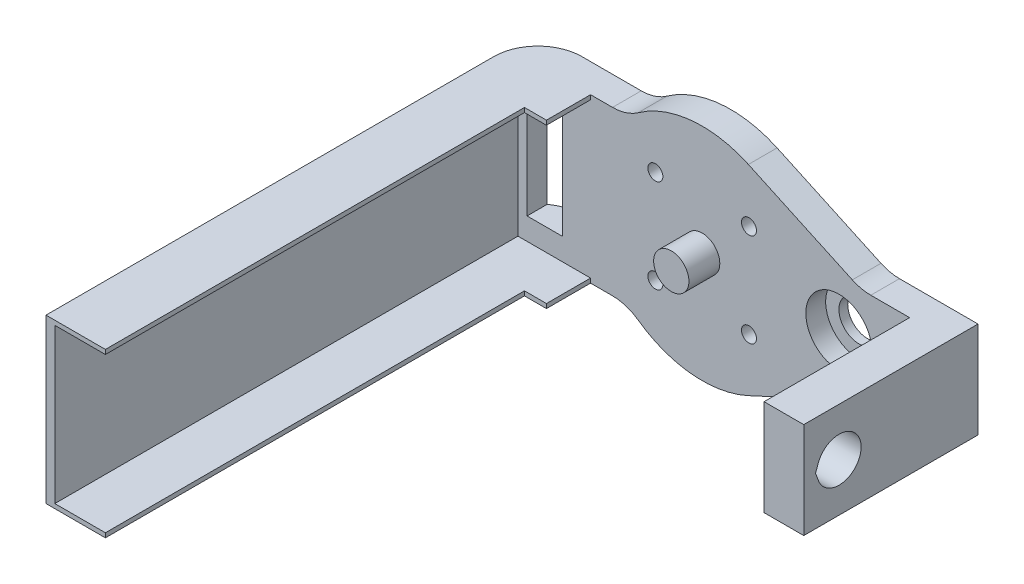
SolidWorks part; units mm, degrees
ref_plane "Front Plane" through (0, 0, 0) normal (0, 0, 1) x (1, 0, 0)
ref_plane "Top Plane" through (0, 0, 0) normal (0, 1, 0) x (1, 0, 0)
ref_plane "Right Plane" through (0, 0, 0) normal (1, 0, 0) x (0, 0, -1)
sketch "Sketch1" plane through (0, 0, 0) normal (0, 0, 1) x (1, 0, 0)
  line L0 (10.4839, 22.6956) -> (36.0323, 10.8939)
  line L1 (36.0323, -10.8939) -> (10.4839, -22.6956)
  circle A0 centre (0, 0) radius 22.215 construction
  circle A1 centre (31, 0) radius 10.2 construction
  arc A2 (10.4839, 22.6956) -> (10.4839, -22.6956) centre (0, 0) ccw
  arc A3 (36.0323, -10.8939) -> (36.0323, 10.8939) centre (31, 0) ccw
  dimension "D1" = 20.4
  dimension "D2" = 44.43
  dimension "D4" = 25
  dimension "D5" = 12
  dimension "D3" = 31
extrude "Boss-Extrude1" add sketch "Sketch1" along normal blind 4.5
sketch "Sketch2" plane through (0, 0, 4.5) normal (0, 0, 1) x (1, 0, 0)
  circle A0 centre (31, 0) radius 7.5
  dimension "D1" = 15
extrude "Cut-Extrude1" cut sketch "Sketch2" against normal through all
sketch "Sketch3" plane through (0, 0, 4.5) normal (0, 0, 1) x (1, 0, 0)
  circle A0 centre (0, 0) radius 4
  dimension "D1" = 8
extrude "Boss-Extrude2" add sketch "Sketch3" along normal blind 7
sketch "Sketch4" plane through (0, 0, 0) normal (0, 0, -1) x (-1, 0, 0)
  line L0 (-36.0323, 10.8939) -> (-56.0323, 10.8939)
  line L1 (-36.0323, -10.8939) -> (-56.0323, -10.8939)
  line L2 (-56.0323, -10.8939) -> (-56.0323, 10.8939)
  line L3 (22.5016, 10.8939) -> (42.5016, 10.8939)
  line L4 (42.5016, 10.8939) -> (42.5016, -10.8939)
  line L5 (42.5016, -10.8939) -> (22.5016, -10.8939)
  arc A0 (-10.4839, -22.6956) -> (-10.4839, 22.6956) centre (0, 0) ccw construction
  arc A1 (22.5016, -10.8939) -> (22.5016, 10.8939) centre (0, 0) ccw
  arc A2 (-36.0323, 10.8939) -> (-36.0323, -10.8939) centre (-31, 0) ccw construction
  arc A3 (-36.0323, 10.8939) -> (-36.0323, -10.8939) centre (-31, 0) ccw
  dimension "D1" = 20
  dimension "D2" = 20
extrude "Boss-Extrude3" add sketch "Sketch4" against normal up to surface (4.5 mm away) up to face at (4, 0, 4.5)
fillet "Fillet1" radius 10 4 edges at (-42.5016, 10.8939, 2.25) (-42.5016, -10.8939, 2.25) (56.0323, -10.8939, 2.25) (56.0323, 10.8939, 2.25)
sketch "Sketch8" plane through (0, 0, 4.5) normal (0, 0, 1) x (1, 0, 0)
  line L0 (56.0323, 0.8939) -> (56.0323, -0.8939) construction
  line L2 (56.0323, 0.8939) -> (56.0323, -0.8939)
  line L3 (55.4014, -4.3896) -> (55.4014, 4.3896)
  line L4 (-42.5016, -0.8939) -> (-42.5016, 0.8939) construction
  line L6 (-42.5016, -0.8939) -> (-42.5016, 0.8939)
  line L7 (-41.8707, 4.3896) -> (-41.8707, -4.3896)
  arc A0 (56.0323, 0.8939) -> (46.0323, 10.8939) centre (46.0323, 0.8939) ccw construction
  arc A1 (46.0323, -10.8939) -> (56.0323, -0.8939) centre (46.0323, -0.8939) ccw construction
  arc A2 (56.0323, 0.8939) -> (55.4014, 4.3896) centre (46.0323, 0.8939) ccw
  arc A3 (55.4014, -4.3896) -> (56.0323, -0.8939) centre (46.0323, -0.8939) ccw
  arc A4 (-32.5016, 10.8939) -> (-42.5016, 0.8939) centre (-32.5016, 0.8939) ccw construction
  arc A5 (-42.5016, -0.8939) -> (-32.5016, -10.8939) centre (-32.5016, -0.8939) ccw construction
  arc A6 (-41.8707, 4.3896) -> (-42.5016, 0.8939) centre (-32.5016, 0.8939) ccw
  arc A7 (-42.5016, -0.8939) -> (-41.8707, -4.3896) centre (-32.5016, -0.8939) ccw
extrude "Cut-Extrude4" cut sketch "Sketch8" against normal through all
sketch "Sketch9" plane through (0, 0, 4.5) normal (0, 0, 1) x (1, 0, 0)
  circle A0 centre (0, 0) radius 15 construction
  circle A1 centre (-10.6066, 10.6066) radius 1
  circle A2 centre (10.6066, 10.6066) radius 1
  circle A3 centre (10.6066, -10.6066) radius 1
  circle A4 centre (-10.6066, -10.6066) radius 1
  point P14 (0, 0)
  dimension "D1" = 30
  dimension "D2" = 2
  dimension "D3" = 4
extrude "Cut-Extrude5" cut sketch "Sketch9" against normal through all
sketch "Sketch10" plane through (0, 0, 4.5) normal (0, 0, 1) x (1, 0, 0)
  circle A0 centre (-10.6066, 10.6066) radius 1.7
  circle A1 centre (10.6066, 10.6066) radius 1.7
  circle A2 centre (10.6066, -10.6066) radius 1.7
  circle A3 centre (-10.6066, -10.6066) radius 1.7
  dimension "D1" = 3.4
extrude "Cut-Extrude6" cut sketch "Sketch10" against normal blind 2.4
sketch "Sketch11" plane through (0, 0, 0) normal (0, 0, -1) x (-1, 0, 0)
  line L0 (-40.9602, 14.6461) -> (-73.6718, 18.9155)
  line L1 (-73.6718, 18.9155) -> (-68.6403, -15.6759)
  line L2 (-68.6403, -15.6759) -> (-41.445, -13.2122)
  arc A0 (-40.9602, 14.6461) -> (-41.445, -13.2122) centre (0, 0) ccw
  dimension "D1" = 87
extrude "Cut-Extrude7" cut sketch "Sketch11" against normal up to surface (4.5 mm away) up to face at (-8.9066, -10.6066, 4.5)
fillet "Fillet2" radius 10 2 edges at (42.1138, -10.8939, 2.25) (42.1138, 10.8939, 2.25)
sketch "Sketch12" plane through (0, 0, 4.5) normal (0, 0, 1) x (1, 0, 0)
  line L0 (-22.5016, 10.8939) -> (-42.5927, 14.8195)
  line L1 (-42.5927, 14.8195) -> (-48.1481, -13.6126)
  line L2 (-48.1481, -13.6126) -> (-27.4273, -14.3153)
  line L3 (-27.4273, -14.3153) -> (-22.5016, -10.8939)
  arc A0 (-22.5016, 10.8939) -> (-22.5016, -10.8939) centre (0, 0) ccw
extrude "Cut-Extrude8" cut sketch "Sketch12" against normal through all
sketch "Sketch23" plane through (0, 0, 0) normal (0, 0, -1) x (-1, 0, 0)
  line L2 (-36.0323, -10.8939) -> (-10.4839, -22.6956)
  line L3 (-10.4839, 22.6956) -> (-36.0323, 10.8939)
  line L4 (-36.0323, -10.8939) -> (-10.4839, -22.6956)
  line L5 (-10.4839, 22.6956) -> (-36.0323, 10.8939)
  circle A0 centre (-10.6066, -10.6066) radius 1 construction
  circle A1 centre (10.6066, -10.6066) radius 1 construction
  circle A2 centre (10.6066, 10.6066) radius 1 construction
  circle A3 centre (-10.6066, 10.6066) radius 1 construction
  arc A4 (-10.4839, -22.6956) -> (-10.4839, 22.6956) centre (0, 0) ccw
  arc A5 (-36.0323, 10.8939) -> (-43.4709, 1.5916) centre (-33.4776, 1.2257) ccw
  arc A6 (-43.4709, 1.5916) -> (-43.4709, -1.5916) centre (0, 0) ccw
  arc A7 (-43.4709, -1.5916) -> (-36.0323, -10.8939) centre (-33.4776, -1.2257) ccw
  arc A8 (-10.4839, -22.6956) -> (-10.4839, 22.6956) centre (0, 0) ccw
  arc A9 (-36.0323, 10.8939) -> (-43.4709, 1.5916) centre (-33.4776, 1.2257) ccw
  arc A10 (-43.4709, 1.5916) -> (-43.4709, -1.5916) centre (0, 0) ccw
  arc A11 (-43.4709, -1.5916) -> (-36.0323, -10.8939) centre (-33.4776, -1.2257) ccw
  circle A12 centre (-10.6066, -10.6066) radius 1
  circle A13 centre (10.6066, -10.6066) radius 1
  circle A14 centre (10.6066, 10.6066) radius 1
  circle A15 centre (-10.6066, 10.6066) radius 1
  circle A16 centre (-31, 0) radius 4.5
  dimension "D2" = 9
  dimension "D1" = 0
extrude "Boss-Extrude6" add sketch "Sketch23" along normal blind 2
sketch "Sketch24" plane through (0, 0, -2) normal (0, 0, -1) x (-1, 0, 0)
  line L0 (-10.6066, 10.6066) -> (10.6066, 10.6066) construction
ref_axis "Axis1" through (10.6066, 10.6066, -2) along (-1, 0, 0)
sketch "Sketch25" plane through (0, 0, -2) normal (0, 0, -1) x (-1, 0, 0)
  line L1 (-36.0323, 10.8939) -> (-56.0323, 10.8939)
  line L3 (-36.0323, -10.8939) -> (-56.0323, -10.8939)
  line L4 (-56.0323, 10.8939) -> (-56.0323, -10.8939)
  arc A0 (-43.4709, -1.5916) -> (-36.0323, -10.8939) centre (-33.4776, -1.2257) ccw construction
  arc A1 (-43.4709, 1.5916) -> (-43.4709, -1.5916) centre (0, 0) ccw construction
  arc A2 (-36.0323, 10.8939) -> (-43.4709, 1.5916) centre (-33.4776, 1.2257) ccw construction
  arc A3 (-43.4709, -1.5916) -> (-36.0323, -10.8939) centre (-33.4776, -1.2257) ccw
  arc A4 (-43.4709, 1.5916) -> (-43.4709, -1.5916) centre (0, 0) ccw
  arc A5 (-36.0323, 10.8939) -> (-43.4709, 1.5916) centre (-33.4776, 1.2257) ccw
  dimension "D1" = 20
extrude "Boss-Extrude7" add sketch "Sketch25" against normal up to surface (6.5 mm away) up to face at (24.5985, 0, 4.5)
sketch "Sketch26" plane through (0, 0, 4.5) normal (0, 0, 1) x (1, 0, 0)
  line L0 (36.0323, 10.8939) -> (56.0323, 10.8939) construction
  line L1 (56.0323, -10.8939) -> (47.0323, -10.8939)
  line L2 (56.0323, -10.8939) -> (56.0323, 10.8939)
  line L3 (56.0323, 10.8939) -> (47.0323, 10.8939)
  line L4 (47.0323, -10.8939) -> (47.0323, 10.8939)
  dimension "D1" = 9
extrude "Boss-Extrude8" add sketch "Sketch26" along normal blind 33
sketch "Sketch27" plane through (56.0323, 0, 0) normal (1, 0, 0) x (0, 0, -1)
  circle A0 centre (-29.5, 0) radius 5
extrude "Cut-Extrude9" cut sketch "Sketch27" against normal up to next
sketch "Sketch28" plane through (0, 0, -2) normal (0, 0, -1) x (-1, 0, 0)
  line L1 (16.8152, 18.5) -> (43.7493, 18.5)
  line L3 (16.8152, -18.5) -> (43.7493, -18.5)
  line L4 (0, 0) -> (47.5, 0) construction
  line L5 (47.5, 0) -> (25.875, 18.5) construction
  line L6 (47.5, 0) -> (31.6196, -18.5) construction
  line L7 (43.7493, -18.5) -> (25, 0) construction
  line L8 (25, 0) -> (43.7493, 18.5) construction
  line L9 (43.7493, 18.5) -> (43.7493, -18.5)
  arc A0 (43.7493, -18.5) -> (43.7493, 18.5) centre (0, 0) ccw construction
  arc A2 (-10.4839, -22.6956) -> (-10.4839, 22.6956) centre (0, 0) ccw construction
  arc A3 (16.8152, -18.5) -> (16.8152, 18.5) centre (0, 0) ccw
  dimension "D1" = 95
  dimension "D3" = 37
extrude "Boss-Extrude9" add sketch "Sketch28" against normal up to surface (6.5 mm away) up to face at (38.5, 0, 4.5)
sketch "Sketch29" plane through (0, 0, 4.5) normal (0, 0, 1) x (1, 0, 0)
  line L0 (-43.7493, 18.5) -> (-30.2822, 18.5)
  line L1 (-43.7493, 18.5) -> (-43.7493, -18.5)
  line L2 (-43.7493, -18.5) -> (-30.2822, -18.5)
  line L3 (-16.8152, -18.5) -> (-43.7493, -18.5) construction
  line L4 (-43.7493, 18.5) -> (-16.8152, 18.5) construction
  line L5 (-41.7493, 16.5) -> (-41.7493, -16.5)
  line L6 (-41.7493, 16.5) -> (-43.7493, 18.5) construction
  line L7 (-41.7493, -16.5) -> (-43.7493, -18.5) construction
  line L8 (-41.7493, 16.5) -> (-30.2822, 16.5)
  line L9 (-30.2822, 16.5) -> (-30.2822, 18.5)
  line L10 (-30.2822, -18.5) -> (-30.2822, -16.5)
  line L11 (-30.2822, -16.5) -> (-41.7493, -16.5)
  dimension "D1" = 33
  dimension "D2" = 2
extrude "Boss-Extrude10" add sketch "Sketch29" along normal blind 105
fillet "Fillet3" radius 10 1 edges at (-43.7493, 0, -2)
fillet "Fillet4" radius 10 4 edges at (36.0323, 10.8939, 1.25) (36.0323, -10.8939, 1.25) (-16.8152, 18.5, 1.25) (-16.8152, -18.5, 1.25)
sketch "Sketch30" plane through (56.0323, 0, 0) normal (1, 0, 0) x (0, 0, -1)
  line L0 (-34.1928, 1.7255) -> (-34.8273, 0)
  line L1 (-34.8273, 0) -> (-34.1928, -1.7255)
  line L2 (-34.5, 0) -> (-34.8273, 0) construction
  circle A0 centre (-29.5, 0) radius 5 construction
  arc A1 (-34.1928, 1.7255) -> (-34.1928, -1.7255) centre (-29.5, 0) ccw
extrude "Cut-Extrude10" cut sketch "Sketch30" against normal up to surface (9 mm away) up to face at (47.0323, 0, 24.5)
sketch "Sketch31" plane through (0, 0, 4.5) normal (0, 0, 1) x (1, 0, 0)
  line L0 (-39.6877, 12.5) -> (-41.7493, 16.5) construction
  line L1 (-39.6877, 12.5) -> (-31.6877, 12.5)
  line L2 (-39.6877, 12.5) -> (-39.6877, -12.5)
  line L3 (-39.6877, -12.5) -> (-31.6877, -12.5)
  line L4 (-31.6877, 12.5) -> (-31.6877, -12.5)
  line L5 (-39.6877, -12.5) -> (-41.7493, -16.5) construction
  dimension "D1" = 25
  dimension "D2" = 8
  dimension "D3" = 4.5
extrude "Cut-Extrude11" cut sketch "Sketch31" against normal through all
sketch "Sketch32" plane through (0, 0, 4.5) normal (0, 0, 1) x (1, 0, 0)
  line L0 (-30.2822, 18.5) -> (-30.2822, 16.5)
  line L1 (-30.2822, 16.5) -> (-27.7493, 16.5)
  line L2 (-27.7493, 16.5) -> (-27.7493, -16.5)
  line L3 (-27.7493, -16.5) -> (-30.2822, -16.5)
  line L4 (-30.2822, -16.5) -> (-30.2822, -18.5)
  line L5 (-30.2822, -18.5) -> (-25.2992, -18.5)
  line L6 (-20.3162, -18.5) -> (-30.2822, -18.5) construction
  line L7 (-25.2992, -18.5) -> (-25.2992, 18.5)
  line L8 (-30.2822, 18.5) -> (-20.3162, 18.5) construction
  line L9 (-25.2992, 18.5) -> (-30.2822, 18.5)
extrude "Boss-Extrude11" add sketch "Sketch32" along normal blind 10
sketch "Sketch33" plane through (-25.2992, 0, 0) normal (1, 0, 0) x (0, 0, -1)
  line L0 (-4.5, -22.6956) -> (-4.5, -11.8156) construction
  line L1 (-14.5, 16.5) -> (-4.5, 16.5)
  line L2 (-14.5, 16.5) -> (-14.5, -16.5)
  line L3 (-14.5, -16.5) -> (-4.5, -16.5)
  line L4 (-4.5, 16.5) -> (-4.5, -16.5)
  line L5 (-109.5, -16.5) -> (-4.5, -16.5) construction
extrude "Cut-Extrude12" cut sketch "Sketch33" against normal up to next
sketch "Sketch34" plane through (-41.7493, 0, 0) normal (1, 0, 0) x (0, 0, -1)
  line L0 (-109.5, 16.5) -> (-109.5, 18.5) construction
  line L1 (-109.5, 17.5) -> (-4.5, 17.5)
  line L2 (-109.5, 17.5) -> (-109.5, -17.5)
  line L3 (-109.5, -17.5) -> (-4.5, -17.5)
  line L4 (-4.5, 17.5) -> (-4.5, -17.5)
  line L5 (-4.5, -18.5) -> (-4.5, -16.5) construction
extrude "Cut-Extrude13" cut sketch "Sketch34" along normal up to surface (16.45 mm away) up to face at (-25.2992, 17.5, 9.5)
